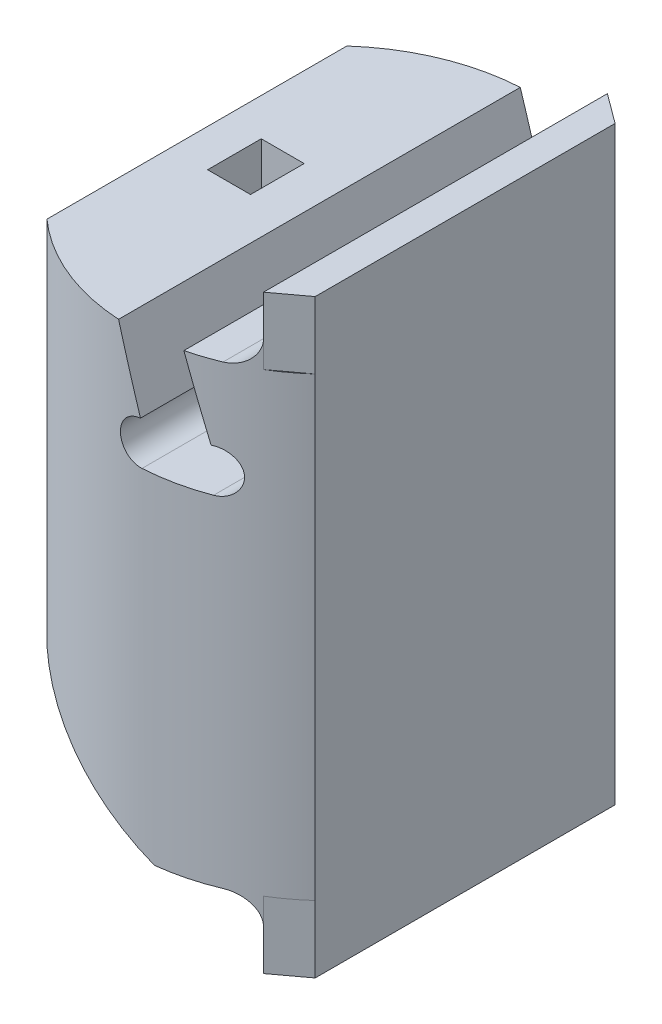
SolidWorks part; units mm, degrees
ref_plane "Front Plane" through (0, 0, 0) normal (0, 0, 1) x (1, 0, 0)
ref_plane "Top Plane" through (0, 0, 0) normal (0, 1, 0) x (1, 0, 0)
ref_plane "Right Plane" through (0, 0, 0) normal (1, 0, 0) x (0, 0, -1)
sketch "Sketch1" plane through (0, 0, 0) normal (0, 0, 1) x (1, 0, 0)
  line L0 (0, 8.5) -> (0, -8.5)
  line L1 (0, -8.5) -> (-7.5, -8.5)
  line L2 (-7.5, -8.5) -> (-7.5, 8.5)
  line L3 (-7.5, 8.5) -> (0, 8.5)
  dimension "D1" = 7.5
  dimension "D2" = 7.5
  dimension "D3" = 17
  dimension "D4" = 8.5
revolve "Revolve1" add sketch "Sketch1" angle 360 about L0
sketch "Sketch2" plane through (0, -8.5, 0) normal (0, -1, 0) x (1, 0, 0)
  line L0 (-5, 5.5902) -> (-5, -5.5902)
  arc A0 (-5, 5.5902) -> (-5, -5.5902) centre (0, 0) ccw
  circle A1 centre (0, 0) radius 7.5 construction
  dimension "D1" = 5
  dimension "D2" = 5
extrude "Cut-Extrude1" cut sketch "Sketch2" against normal blind 20
sketch "Sketch4" plane through (0, -8.5, 0) normal (0, -1, 0) x (1, 0, 0)
  line L0 (-3.6, 1) -> (-3.6, -1)
  line L1 (-3.6, 1) -> (-2, 1)
  line L2 (-3.6, -1) -> (-2, -1)
  line L3 (-2, 1) -> (-2, -1)
  line L4 (-3.6, 1) -> (-2, -1) construction
  line L5 (-3.6, -1) -> (-2, 1) construction
  point P1 (-2.8, 0)
  dimension "D1" = 2
  dimension "D2" = 1.6
  dimension "D3" = 1
  dimension "D4" = 2
extrude "Cut-Extrude2" cut sketch "Sketch4" against normal blind 20
mirror "Mirror1" about plane through (0, 0, 0) normal (1, 0, 0) of "Cut-Extrude1"
sketch "Sketch7" plane through (0, 0, 0) normal (0, 0, 1) x (1, 0, 0)
  line L2 (0.4413, 4.1212) -> (2.6413, 4.1212)
  line L4 (5, 8.5) -> (-5, 8.5) construction
  line L6 (1.7963, 8.5) -> (2.5739, 5.7184)
  line L7 (0.388, 5.7194) -> (-0.4316, 8.5)
  line L8 (-0.4316, 8.5) -> (1.7963, 8.5)
  arc A0 (0.388, 5.7194) -> (-0.3576, 4.88) centre (0.4413, 4.9212) ccw
  arc A1 (-0.3576, 4.88) -> (0.4413, 4.1212) centre (0.4413, 4.9212) ccw
  arc A2 (2.6413, 4.1212) -> (3.1806, 4.3303) centre (2.6413, 4.9212) ccw
  arc A3 (3.1806, 4.3303) -> (2.5739, 5.7184) centre (2.6413, 4.9212) ccw
  dimension "D1" = 0.8
  dimension "D2" = 0.8
  dimension "D3" = 0.8
  dimension "D4" = 0.8
  dimension "D5" = 2.2
extrude "Cut-Extrude3" cut sketch "Sketch7" along normal through all both and the other way through all
sketch "Sketch8" plane through (0, 0, 0) normal (0, 0, 1) x (1, 0, 0)
  line L0 (-5, -5.2689) -> (0.8677, -8.5)
  line L1 (-5, -8.5) -> (-5, 8.5) construction
  line L2 (-5, -8.5) -> (5, -8.5) construction
  line L3 (0.8677, -8.5) -> (-5, -8.5)
  line L4 (-5, -8.5) -> (-5, -5.2689)
extrude "Cut-Extrude4" cut sketch "Sketch8" against normal through all both and the other way through all
sketch "Sketch13" plane through (0, 8.5, 0) normal (0, 1, 0) x (1, 0, 0)
  line L0 (5, 5.5902) -> (5, -5.5902)
  line L1 (5, -5.5902) -> (3.8949, -6.4094)
  line L2 (3.8949, -6.4094) -> (3.8949, 6.4094)
  line L3 (3.8949, 6.4094) -> (5, 5.5902)
  arc A0 (1.7963, -7.2817) -> (5, -5.5902) centre (0, 0) ccw construction
  arc A1 (5, 5.5902) -> (1.7963, 7.2817) centre (0, 0) ccw construction
extrude "Boss-Extrude4" add sketch "Sketch13" along normal blind 2.5
fillet "Fillet1" radius 1 1 edges at (3.8949, 8.5, 0)
sketch "Sketch15" plane through (0, -8.5, 0) normal (0, -1, 0) x (1, 0, 0)
  line L0 (5, 5.5902) -> (5, -5.5902)
  line L1 (5, -5.5902) -> (3.8949, -6.4094)
  line L2 (3.8949, -6.4094) -> (3.8949, 6.4094)
  line L3 (3.8949, 6.4094) -> (5, 5.5902)
extrude "Boss-Extrude7" add sketch "Sketch15" along normal blind 2.5
fillet "Fillet5" radius 1 1 edges at (3.8949, -8.5, 0)
equation "\"mm\"=3.04027"
